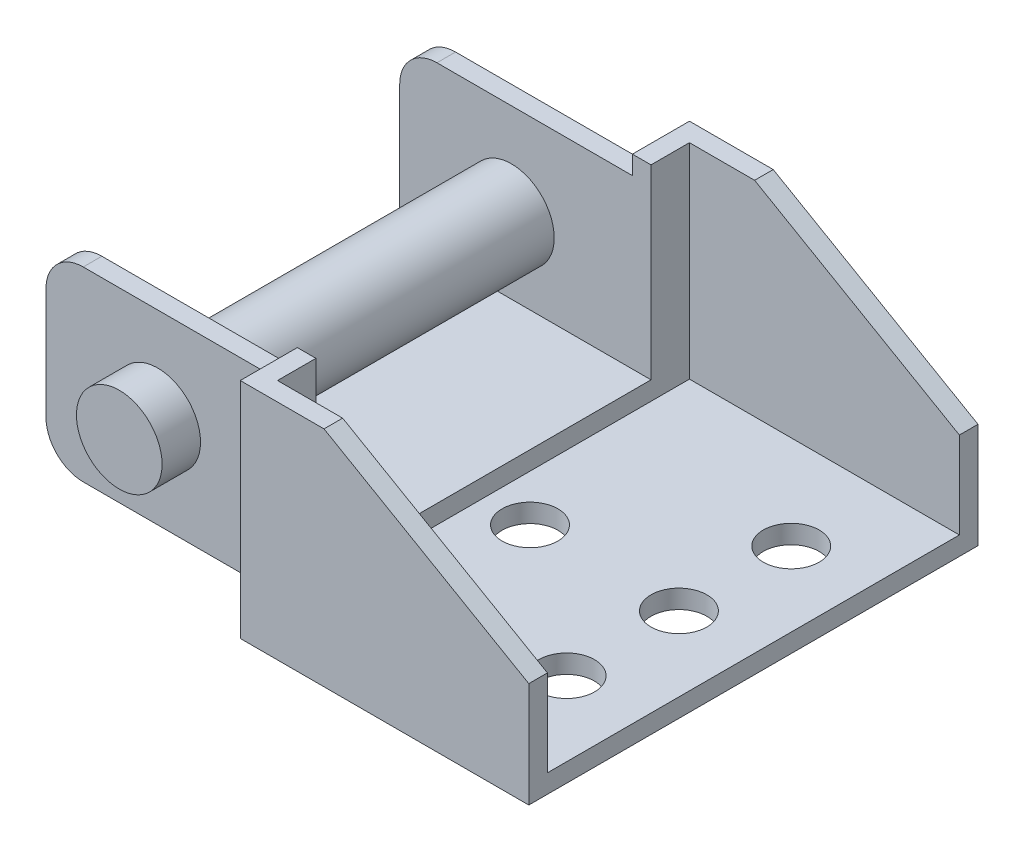
SolidWorks part; units mm, degrees
ref_plane "Front Plane" through (0, 0, 0) normal (0, 0, 1) x (1, 0, 0)
ref_plane "Top Plane" through (0, 0, 0) normal (0, 1, 0) x (1, 0, 0)
ref_plane "Right Plane" through (0, 0, 0) normal (1, 0, 0) x (0, 0, -1)
sketch "Sketch1" plane through (0, 0, 0) normal (0, 0, 1) x (1, 0, 0)
  line L0 (22, -6) -> (0, -6)
  line L1 (0, 6) -> (11, 6)
  line L2 (11, 6) -> (22, -0.3509)
  line L3 (22, -0.3509) -> (22, -6)
  line L5 (-6, 6) -> (0, 6)
  line L9 (-6, -6) -> (-6, 6)
  line L10 (-6, -6) -> (0, -6)
  circle A0 centre (0, 0) radius 2.3
  arc A1 (0, -6) -> (0, 6) centre (0, 0) cw construction
  dimension "D4" = 4.6
  dimension "D1" = 22
  dimension "D2" = 12
  dimension "D3" = 30
  dimension "D5" = 11
extrude "Boss-Extrude1" add sketch "Sketch1" along normal mid plane 24.13
sketch "Sketch2" plane through (0, 6, 0) normal (0, 1, 0) x (1, 0, 0)
  line L0 (0, 12.065) -> (0, -12.065) construction
  line L1 (11, 12.065) -> (-6, 12.065) construction
  line L2 (11, -12.065) -> (-6, -12.065) construction
  line L3 (-6, -12.065) -> (-6, 12.065) construction
  line L4 (-6, -11.065) -> (6.5, -11.065)
  line L5 (-6, -11.065) -> (-6, 11.065)
  line L6 (-6, 11.065) -> (6.5, 11.065)
  line L7 (6.5, -11.065) -> (6.5, 11.065)
  line L8 (22, 12.065) -> (11, 12.065) construction
  line L9 (22, -12.065) -> (11, -12.065) construction
  line L10 (22, -12.065) -> (22, 12.065) construction
  line L11 (0, -12.065) -> (0, 12.065) construction
  line L12 (18, -12.065) -> (18, -6.0325) construction
  line L14 (10, -12.065) -> (10, 12.065) construction
  line L15 (18, 6.0325) -> (18, 12.065) construction
  line L16 (18, -6.0325) -> (18, 0) construction
  line L17 (18, 0) -> (18, 6.0325) construction
  circle A0 centre (18, 0) radius 1.5
  circle A1 centre (10, 0) radius 1.5
  circle A2 centre (18, 6.0325) radius 1.5
  circle A3 centre (18, -6.0325) radius 1.5
  dimension "D3" = 3
  dimension "D1" = 4
  dimension "D2" = 8
  dimension "D4" = 1
  dimension "D5" = 1
  dimension "D6" = 3.5
extrude "Cut-Extrude1" [suppressed] cut sketch "Sketch2" against normal through all
sketch "Sketch4" [suppressed] plane through (6.5, 0, 0) normal (-1, 0, 0) x (0, 0, 1)
  line L0 (11.065, -6) -> (11.065, 6) construction
  line L1 (-11.065, 6) -> (11.065, 6)
  line L2 (-11.065, 6) -> (-11.065, -5)
  line L3 (-11.065, -5) -> (11.065, -5)
  line L4 (11.065, 6) -> (11.065, -5)
  line L5 (11.065, -6) -> (-11.065, -6) construction
  dimension "D1" = 1
extrude "Cut-Extrude2" [suppressed] cut sketch "Sketch4" against normal through all
sketch "Sketch5" plane through (0, 6, 0) normal (0, 1, 0) x (1, 0, 0)
  line L2 (-6, -10) -> (6.5, -10)
  line L3 (-6, 10) -> (6.5, 10)
  line L4 (6.5, 10) -> (6.5, 12.065)
  line L5 (11, 12.065) -> (-6, 12.065) construction
  line L6 (6.5, 12.065) -> (-6, 12.065)
  line L7 (-6, 12.065) -> (-6, 10)
  line L8 (6.5, -10) -> (6.5, -12.065)
  line L9 (11, -12.065) -> (-6, -12.065) construction
  line L10 (6.5, -12.065) -> (-6, -12.065)
  line L11 (-6, -12.065) -> (-6, -10)
  line L12 (6.5, -11.065) -> (6.5, 11.065) construction
  circle A0 centre (18, 6.0325) radius 1.5 construction
  circle A1 centre (18, 0) radius 1.5 construction
  circle A2 centre (18, -6.0325) radius 1.5 construction
  circle A3 centre (10, 0) radius 1.5 construction
  circle A4 centre (18, 6.0325) radius 1.5
  circle A5 centre (18, 0) radius 1.5
  circle A6 centre (18, -6.0325) radius 1.5
  circle A7 centre (10, 0) radius 1.5
  dimension "D1" = 20
fillet "Fillet2" [suppressed] radius 2
extrude "Cut-Extrude3" cut sketch "Sketch5" against normal through all
sketch "Sketch6" plane through (-6, 0, 0) normal (-1, 0, 0) x (0, 0, 1)
  line L5 (10, 6) -> (-10, 6) construction
  line L14 (-9, 6) -> (9, 6)
  line L15 (-9, 6) -> (-9, -4)
  line L16 (-9, -4) -> (9, -4)
  line L17 (9, 6) -> (9, -4)
  line L18 (-10, -6) -> (-10, 6) construction
  line L19 (10, -6) -> (10, 6) construction
  line L20 (10, -6) -> (-10, -6) construction
  line L22 (-10, -6) -> (10, -6)
  line L23 (-10, -6) -> (-10, -5)
  line L24 (-10, -5) -> (10, -5)
  line L25 (10, -6) -> (10, -5)
  line M11 (10, 6) -> (-10, 6)
  dimension "D1" = 1
  dimension "D2" = 1
  dimension "D3" = 2
  dimension "D4" = 1
extrude "Cut-Extrude5" cut sketch "Sketch6" against normal through all contours L17 L15 L16 M11
sketch "Sketch9" plane through (-6, 0, 0) normal (-1, 0, 0) x (0, 0, 1)
  line L0 (10, -6) -> (10, 6) construction
  line L1 (-10, -6) -> (10, -6)
  line L2 (-10, -6) -> (-10, -5)
  line L3 (-10, -5) -> (10, -5)
  line L4 (10, -6) -> (10, -5)
  dimension "D1" = 1
extrude "Cut-Extrude8" cut sketch "Sketch9" against normal up to surface (12.5 mm away) up to face at (6.5, 0, 11.0325)
sketch "Sketch7" plane through (0, 0, 12.065) normal (0, 0, 1) x (1, 0, 0)
  circle A0 centre (0, 0) radius 2.3 construction
  circle A1 centre (0, 0) radius 2.3
extrude "Boss-Extrude2" add sketch "Sketch7" against normal up to surface (24.13 mm away) up to face at (13.6, -0.0702, -12.065)
sketch "Sketch8" plane through (0, 6, 0) normal (0, 1, 0) x (1, 0, 0)
  line L1 (-6, -9) -> (-6, -10) construction
  line L2 (-6, -10) -> (6.5, -10) construction
  line L3 (6.5, -10) -> (6.5, -12.065) construction
  line L4 (6.5, -12.065) -> (11, -12.065) construction
  line L5 (11, -12.065) -> (11, -9) construction
  line L6 (-6, 10) -> (-6, 9) construction
  line L8 (11, 9) -> (11, 12.065) construction
  line L9 (11, 12.065) -> (6.5, 12.065) construction
  line L10 (6.5, 12.065) -> (6.5, 10) construction
  line L11 (6.5, 10) -> (-6, 10) construction
  line L12 (11, -9) -> (-6, -9)
  line L13 (-6, -9) -> (-6, -10)
  line L14 (-6, -10) -> (6.5, -10)
  line L15 (6.5, -10) -> (6.5, -12.065)
  line L16 (6.5, -12.065) -> (11, -12.065)
  line L17 (11, -12.065) -> (11, -9)
  line L18 (-6, 10) -> (-6, 9)
  line L19 (-6, 9) -> (11, 9)
  line L20 (11, 9) -> (11, 12.065)
  line L21 (11, 12.065) -> (6.5, 12.065)
  line L22 (6.5, 12.065) -> (6.5, 10)
  line L23 (6.5, 10) -> (-6, 10)
  line L24 (6.5, 10) -> (6.5, 9)
  line L26 (6.5, -9) -> (6.5, -10)
  line M1 (-6, 10) -> (-6, 9)
  line M6 (6.5, 10) -> (-6, 10)
extrude "Cut-Extrude6" cut sketch "Sketch8" against normal blind 1 contours L26 L12 L13 L14 | L24 M6 M1 region at (0.25, 6, 9.5) region at (0.25, 6, -9.5)
fillet "Fillet3" radius 2 3 edges at (-6, -5, 0) (-6, 5, -9.5) (-6, 5, 9.5)
sketch "Sketch10" plane through (22, 0, 0) normal (1, 0, 0) x (0, 0, -1)
  line L0 (-12.065, 6) -> (-9, 6) construction
  line L2 (-9, -4) -> (-9, 6)
  line L3 (-9, 6) -> (-11.065, 6)
  line L4 (-11.065, -4) -> (-11.065, 6)
  line L7 (9, -4) -> (9, 6)
  line L8 (9, 6) -> (11.065, 6)
  line L9 (11.065, -4) -> (11.065, 6)
  line L10 (-12.065, -0.3509) -> (-12.065, 6) construction
  line L11 (9, 6) -> (12.065, 6) construction
  line L12 (-12.065, -6) -> (12.065, -6) construction
  line L13 (-9, -4) -> (9, -4)
  line L14 (-11.065, -4) -> (-11.065, -5)
  line L15 (-11.065, -5) -> (11.065, -5)
  line L16 (11.065, -4) -> (11.065, -5)
  point P17 (10.5325, 6)
  dimension "D1" = 1
  dimension "D2" = 1
extrude "Cut-Extrude9" cut sketch "Sketch10" against normal offset from surface (14.5 mm away) 1 up to face at (6.5, 1.8333, 0)
